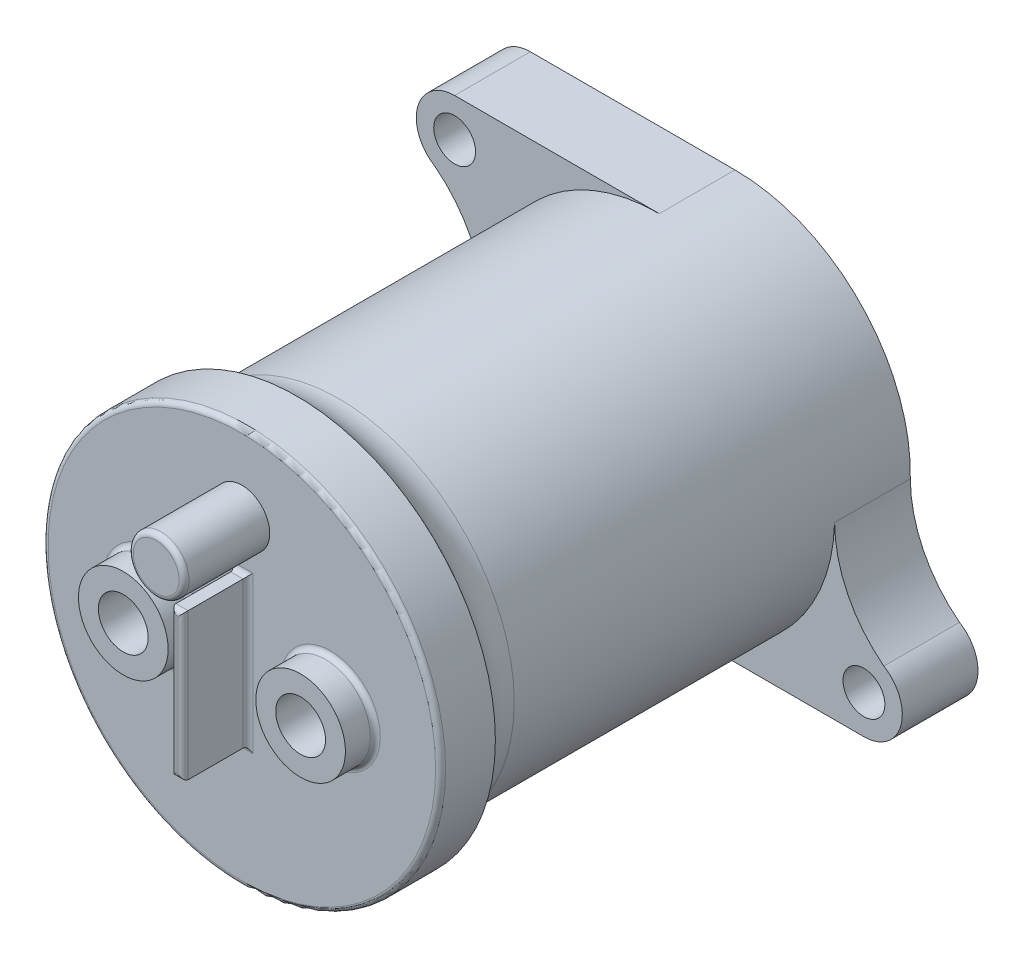
SolidWorks part; units mm, degrees
material "Custom Plastic"
ref_plane "X-Y Datum" through (0, 0, 0) normal (0, 0, 1) x (1, 0, 0)
ref_plane "X-Z Datum" through (0, 0, 0) normal (0, 1, 0) x (1, 0, 0)
ref_plane "Y-Z Datum" through (0, 0, 0) normal (1, 0, 0) x (0, 0, -1)
sketch "Sketch2" plane through (0, 0, 0) normal (0, 0, 1) x (1, 0, 0)
  circle A0 centre (0, 0) radius 17.6
  dimension "D1" = 35.2
extrude "Boss-Extrude1" add sketch "Sketch2" along normal blind 52.5
sketch "Sketch3" plane through (0, 0, 0) normal (0, 0, 1) x (1, 0, 0)
  line L0 (-17.6, 0) -> (17.6, 0) construction
  line L2 (19.36, 0) -> (-19.36, 0) construction
  line L4 (0, 17.6) -> (0, -17.6) construction
  line L5 (-20.5412, 17.6) -> (0, 17.6)
  line L7 (-17.6, 0) -> (17.6, 0) construction
  line L8 (0, -17.6) -> (20.5412, -17.6)
  line L9 (0, -19.36) -> (0, 19.36) construction
  arc A6 (17.5941, -0.4546) -> (17.6, 0) centre (30.3137, -0.3916) cw
  arc A7 (17.5941, 0.4546) -> (17.6, 0) centre (30.3137, 0.3916) ccw
  circle A8 centre (0, 0) radius 17.6
  circle A9 centre (0, 0) radius 17.6
  arc A18 (-17.5941, -0.4546) -> (-17.6, 0) centre (-30.3137, -0.3916) ccw
  circle A19 centre (-20.5412, 13.75) radius 2.1
  circle A20 centre (-20.5412, 13.75) radius 3.85
  arc A21 (-22.5405, 10.4598) -> (-17.6, 0) centre (-30.3137, 0.3916) cw
  circle A22 centre (20.5412, -13.75) radius 2.1
  circle A23 centre (20.5412, -13.75) radius 3.85
  arc A24 (22.5405, -10.4598) -> (17.6, 0) centre (30.3137, -0.3916) cw
  point P4 (0, 0)
  point P10 (0, 0)
  point P23 (0, 0)
  dimension "D4" = 0
extrude "Boss-Extrude2" add sketch "Sketch3" along normal blind 7.6 contours A9 | A9 | A9 | A9 | A9 | A9 | A20 A19 | A23 A22 region at (-14.5084, 12.7029, 0) region at (-17.8959, 16.3954, 0) region at (14.5084, -12.7029, 0) region at (23.8019, -11.9159, 0)
sketch "Sketch4" plane through (0, 0, 52.5) normal (0, 0, 1) x (1, 0, 0)
  line L0 (-8.9, 0) -> (8.9, 0) construction
  line L1 (-0.615, 7.35) -> (0.615, 7.35)
  line L2 (-0.615, 7.35) -> (-0.615, -7.35)
  line L3 (-0.615, -7.35) -> (0.615, -7.35)
  line L4 (0.615, 7.35) -> (0.615, -7.35)
  line L5 (-0.615, 7.35) -> (0.615, -7.35) construction
  line L6 (-0.615, -7.35) -> (0.615, 7.35) construction
  circle A0 centre (-8.9, 0) radius 2.5
  circle A1 centre (8.9, 0) radius 2.5
  circle A2 centre (-8.9, 0) radius 4.5
  circle A3 centre (8.9, 0) radius 4.5
  point P0 (0, 0)
  point P11 (0, 0)
  dimension "D4" = 5
  dimension "D5" = 9
  dimension "D1" = 1.23
  dimension "D2" = 14.7
  dimension "D3" = 17.8
extrude "Boss-Extrude3" add sketch "Sketch4" along normal blind 3.5 contours L2 L1 L4 L3
sketch "Sketch5" plane through (0, 0, 52.5) normal (0, 0, 1) x (1, 0, 0)
  line L4 (0.615, 7.35) -> (-0.615, 7.35)
  line L5 (0.615, -7.35) -> (0.615, 7.35)
  line L6 (-0.615, -7.35) -> (0.615, -7.35)
  line L7 (-0.615, 7.35) -> (-0.615, -7.35)
  line L8 (0.615, 7.35) -> (-0.615, 7.35)
  line L9 (0.615, -7.35) -> (0.615, 7.35)
  line L10 (-0.615, -7.35) -> (0.615, -7.35)
  line L11 (-0.615, 7.35) -> (-0.615, -7.35)
  circle A1 centre (8.9, 0) radius 4.5
  circle A2 centre (8.9, 0) radius 4.5
  circle A3 centre (-8.9, 0) radius 4.5
  circle A4 centre (-8.9, 0) radius 4.5
  circle A5 centre (8.9, 0) radius 2.5
  circle A6 centre (8.9, 0) radius 2.5
  circle A7 centre (-8.9, 0) radius 2.5
  circle A8 centre (-8.9, 0) radius 2.5
  circle M22 centre (0, 0) radius 17.6
  line M23 (0.615, 7.35) -> (0.615, -7.35)
  line M24 (0.615, -7.35) -> (-0.615, -7.35)
  line M25 (-0.615, -7.35) -> (-0.615, 7.35)
  line M26 (-0.615, 7.35) -> (0.615, 7.35)
  dimension "D1" = 0
  dimension "D2" = 0
  dimension "D3" = 0
  dimension "D4" = 0
  dimension "D5" = 0
extrude "Cut-Extrude1" cut sketch "Sketch5" against normal blind 3 contours A4 A2 M22 M26 M23 M24 M25 | A8 | A6 region at (8.9, 0, 52.5) region at (-8.9, 0, 52.5) region at (-17.1022, 0, 52.5)
sketch "Sketch7" plane through (0, 0, 49.5) normal (0, 0, 1) x (1, 0, 0)
  circle A0 centre (0, 0) radius 19.95
  dimension "D1" = 39.9
extrude "Boss-Extrude5" add sketch "Sketch7" against normal blind 5.5
fillet "Fillet3" radius 5 1 edges at (17.6, 0, 44)
fillet "Fillet4" radius 0.5 11 edges at (-0.615, 0, 56) (0, 7.35, 56) (0.615, 0, 56) (0, -7.35, 56) (19.95, 0, 49.5) (-0.615, 0, 49.5) (0, -7.35, 49.5) (0.615, 0, 49.5) (0, 7.35, 49.5) (13.4, 0, 49.5) (-4.4, 0, 49.5)
sketch "Sketch8" plane through (0, 0, 52.5) normal (0, 0, 1) x (1, 0, 0)
  circle A0 centre (-8.9, 0) radius 2.5 construction
  circle A1 centre (8.9, 0) radius 2.5
  circle A2 centre (8.9, 0) radius 2.5
  circle A3 centre (-8.9, 0) radius 2.5
  dimension "D1" = 0
extrude "Cut-Extrude2" cut sketch "Sketch8" against normal blind 7
ref_plane "Plane1" through (0, 0, 0) normal (0.8035, 0.5952, 0) x (0, 0, 1)
sketch "Sketch10" plane through (0, 0, 49.5) normal (0, 0, 1) x (1, 0, 0)
  line L0 (0, 0) -> (0, 12.15) construction
  line L1 (0.615, 7.35) -> (-0.615, 7.35) construction
  circle A0 centre (0, 12.15) radius 2.8
  point P2 (0, 9.35)
  dimension "D1" = 5.6
  dimension "D2" = 2
extrude "Boss-Extrude6" add sketch "Sketch10" along normal blind 8.6
fillet "Fillet5" radius 0.5 1 edges at (2.8, 12.15, 58.1)
